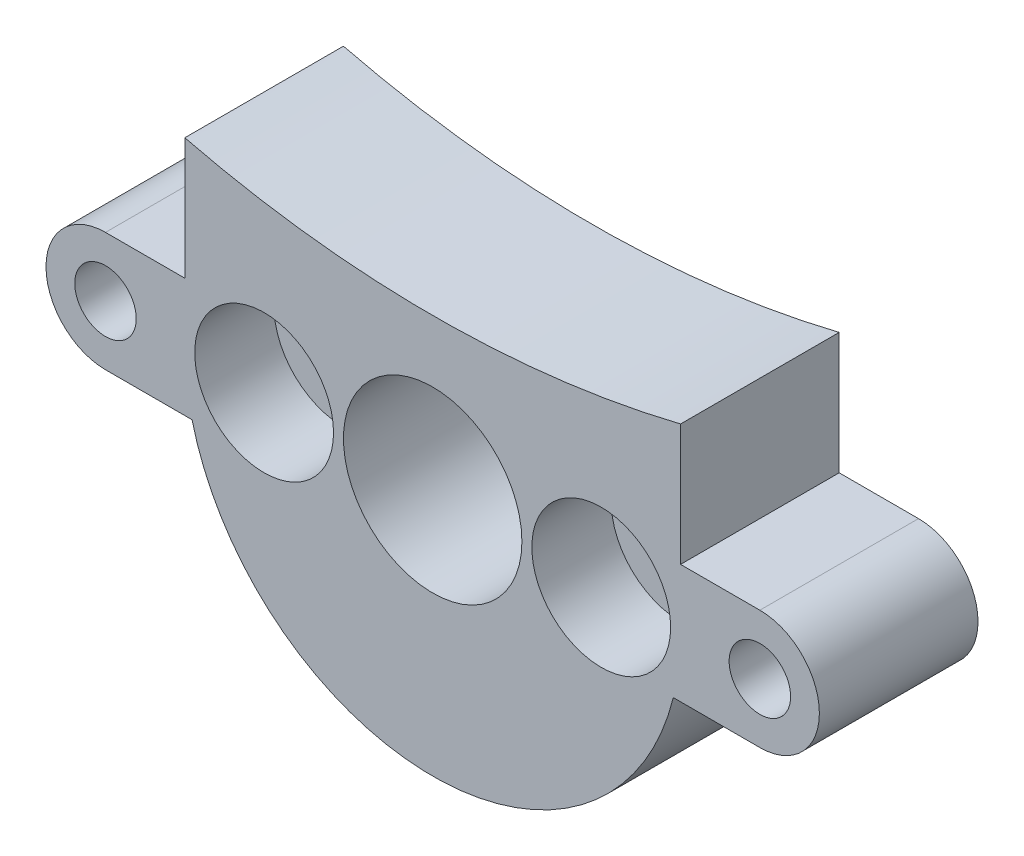
SolidWorks part; units mm, degrees
ref_plane "Front Plane" through (0, 0, 0) normal (0, 0, 1) x (1, 0, 0)
ref_plane "Top Plane" through (0, 0, 0) normal (0, 1, 0) x (1, 0, 0)
ref_plane "Right Plane" through (0, 0, 0) normal (1, 0, 0) x (0, 0, -1)
sketch "Sketch1" plane through (0, 0, 0) normal (0, 0, 1) x (1, 0, 0)
  line L0 (-8.5, 0) -> (8.5, 0) construction
  line L1 (0, 0) -> (0, 60) construction
  line L6 (-8.5, 0) -> (-16.5, 0) construction
  line L7 (8.5, 0) -> (16.5, 0) construction
  line L8 (-16.5, 3) -> (-12.5, 3)
  line L10 (16.5, 3) -> (12.5, 3)
  line L12 (-12.5, 9.1325) -> (-12.5, 3)
  line L13 (12.5, 3) -> (12.5, 9.1325)
  line L14 (16.5, -3) -> (12.1347, -3)
  line L15 (-16.5, -3) -> (-12.1347, -3)
  circle A0 centre (-8.5, 0) radius 1.55
  circle A1 centre (8.5, 0) radius 1.55
  circle A4 centre (0, 60) radius 52.3808 construction
  circle A8 centre (0, 0) radius 4.5
  arc A16 (-12.5, 0) -> (12.5, 0) centre (0, 0) ccw construction
  arc A17 (-12.5, 9.1325) -> (12.5, 9.1325) centre (0, 60) ccw
  circle A18 centre (-16.5, 0) radius 1.55
  circle A19 centre (16.5, 0) radius 1.55
  arc A21 (-16.5, 3) -> (-16.5, -3) centre (-16.5, 0) ccw
  arc A24 (16.5, 3) -> (16.5, -3) centre (16.5, 0) cw
  arc A25 (-12.1347, -3) -> (12.1347, -3) centre (0, 0) ccw
  point P4 (0, 0)
  point P13 (0, 7.6192)
  point P28 (0, 0)
extrude "Boss-Extrude1" add sketch "Sketch1" along normal blind 8
sketch "Sketch2" plane through (0, 0, 8) normal (0, 0, 1) x (1, 0, 0)
  circle A0 centre (-8.5, 0) radius 3.5
  circle A1 centre (8.5, 0) radius 3.5
extrude "Cut-Extrude1" cut sketch "Sketch2" against normal blind 4
